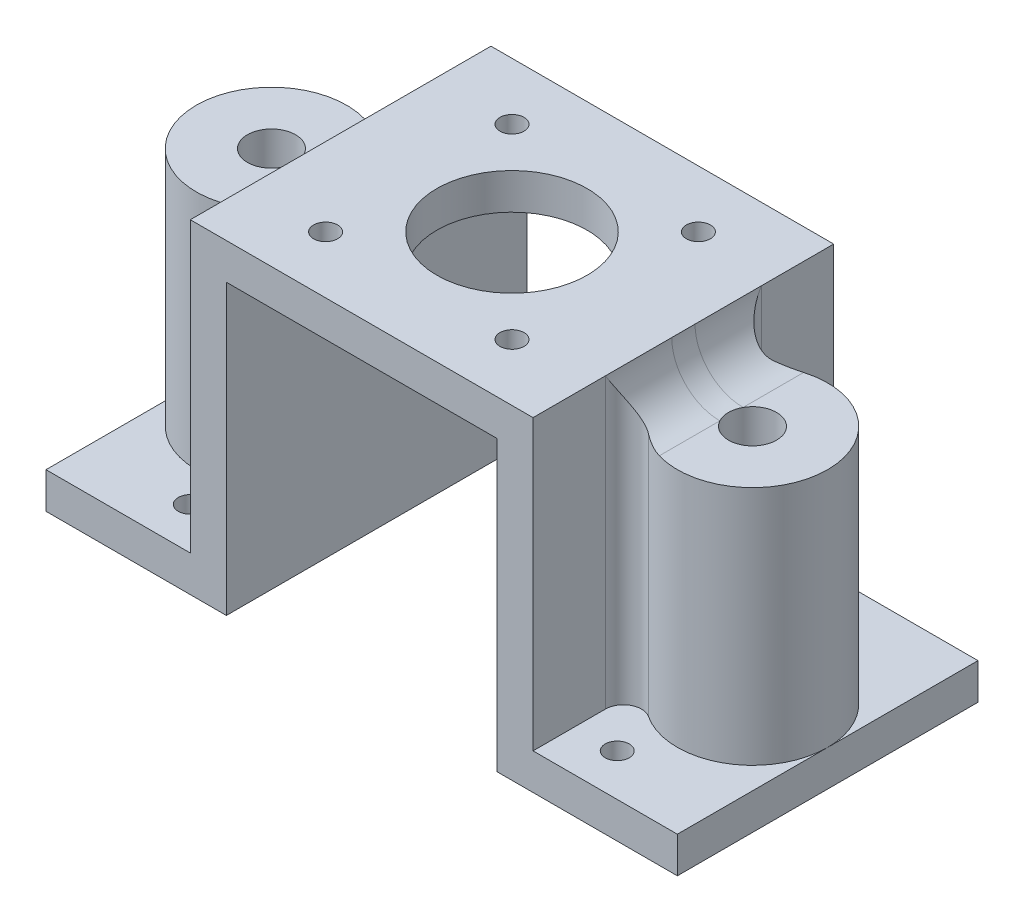
SolidWorks part; units mm, degrees
material "ABS"
ref_plane "Plano frontal" through (0, 0, 0) normal (0, 0, 1) x (1, 0, 0)
ref_plane "Plano superior" through (0, 0, 0) normal (0, 1, 0) x (1, 0, 0)
ref_plane "Plano direito" through (0, 0, 0) normal (1, 0, 0) x (0, 0, -1)
sketch "Esboço1" plane through (0, 0, 0) normal (0, 0, 1) x (1, 0, 0)
  line L0 (-28.5, 54) -> (28.5, 54)
  line L1 (28.5, 54) -> (28.5, 6)
  line L2 (52.5, 6) -> (28.5, 6)
  line L3 (52.5, 6) -> (52.5, 0)
  line L4 (52.5, 0) -> (22.5, 0)
  line L5 (22.5, 0) -> (22.5, 48)
  line L6 (22.5, 48) -> (-22.5, 48)
  line L7 (28.5, 6) -> (22.5, 6) construction
  line L8 (22.5, 48) -> (22.5, 54) construction
  line L9 (0, 63.425) -> (0, 0) construction
  line L10 (-22.5, 48) -> (-22.5, 54) construction
  line L11 (-28.5, 6) -> (-22.5, 6) construction
  line L12 (-22.5, 0) -> (-22.5, 48)
  line L13 (-52.5, 0) -> (-22.5, 0)
  line L14 (-52.5, 6) -> (-52.5, 0)
  line L15 (-52.5, 6) -> (-28.5, 6)
  line L16 (-28.5, 54) -> (-28.5, 6)
  point P19 (0, 48)
  point P23 (0, 54)
  dimension "D1" = 48
  dimension "D2" = 6
  dimension "D3" = 45
  dimension "D4" = 105
extrude "Ressalto-extrusão1" add sketch "Esboço1" along normal mid plane 50
sketch "Esboço2" plane through (0, 54, 0) normal (0, 1, 0) x (1, 0, 0)
  line L0 (0, 25) -> (0, -25) construction
  line L1 (28.5, 25) -> (-28.5, 25) construction
  line L2 (28.5, -25) -> (-28.5, -25) construction
  line L4 (-15.5, 15.5) -> (15.5, 15.5) construction
  line L5 (-15.5, 15.5) -> (-15.5, -15.5) construction
  line L6 (-15.5, -15.5) -> (15.5, -15.5) construction
  line L7 (15.5, 15.5) -> (15.5, -15.5) construction
  line L8 (-15.5, 15.5) -> (15.5, -15.5) construction
  line L9 (-15.5, -15.5) -> (15.5, 15.5) construction
  circle A0 centre (0, 0) radius 12.5
  circle A1 centre (-15.5, 15.5) radius 2
  circle A2 centre (15.5, 15.5) radius 2
  circle A3 centre (15.5, -15.5) radius 2
  circle A4 centre (-15.5, -15.5) radius 2
  dimension "D1" = 4
  dimension "D3" = 25
  dimension "D2" = 31
extrude "Corte-extrusão1" cut sketch "Esboço2" against normal blind 42
sketch "Esboço3" plane through (0, 6, 0) normal (0, 1, 0) x (1, 0, 0)
  line L0 (27.7526, 2.5) -> (28.5, 2.5)
  line L2 (0, 35.3204) -> (0, -32.8451) construction
  line L3 (0, 0) -> (71.2121, 0) construction
  line L4 (27.7526, -2.5) -> (28.5, -2.5)
  line L6 (28.5, -2.5) -> (28.5, 2.5)
  line L7 (-27.7526, -2.5) -> (-28.5, -2.5)
  line L8 (-28.5, -2.5) -> (-28.5, 2.5)
  line L9 (-27.7526, 2.5) -> (-28.5, 2.5)
  line L10 (28.5, -25) -> (28.5, 25) construction
  arc A0 (27.7526, -2.5) -> (27.7526, 2.5) centre (40, 0) ccw
  circle A1 centre (40, 0) radius 4
  circle A2 centre (-40, 0) radius 4
  arc A3 (-27.7526, -2.5) -> (-27.7526, 2.5) centre (-40, 0) cw
  dimension "D2" = 25
  dimension "D3" = 8
  dimension "D1" = 5
  dimension "D4" = 40
extrude "Ressalto-extrusão2" add sketch "Esboço3" along normal blind 40
fillet "Filete1" radius 8 2 edges at (-28.5, 46, 0) (28.5, 46, 0)
sketch "Esboço4" plane through (0, 6, 0) normal (0, 1, 0) x (1, 0, 0)
  line L0 (-35.5, 18) -> (-35.5, 25) construction
  line L1 (-28.5, 25) -> (-52.5, 25) construction
  line L2 (-35.5, 18) -> (-52.5, 18) construction
  line L3 (-52.5, -25) -> (-52.5, 0) construction
  line L4 (-59.6325, 0) -> (0, 0) construction
  line L5 (0, 0) -> (0, 35.3341) construction
  circle A0 centre (-35.5, 18) radius 2
  circle A1 centre (-35.5, 18) radius 5.5 construction
  circle A2 centre (35.5, 18) radius 2
  circle A3 centre (35.5, -18) radius 2
  circle A4 centre (-35.5, -18) radius 2
  dimension "D1" = 4
  dimension "D2" = 11
  dimension "D3" = 7
  dimension "D4" = 17
extrude "Corte-extrusão2" cut sketch "Esboço4" against normal through all
fillet "Filete5" radius 3 4 edges at (-28.5, 30, -4.899) (-28.5, 30, 4.899) (28.5, 30, -4.899) (28.5, 30, 4.899)
